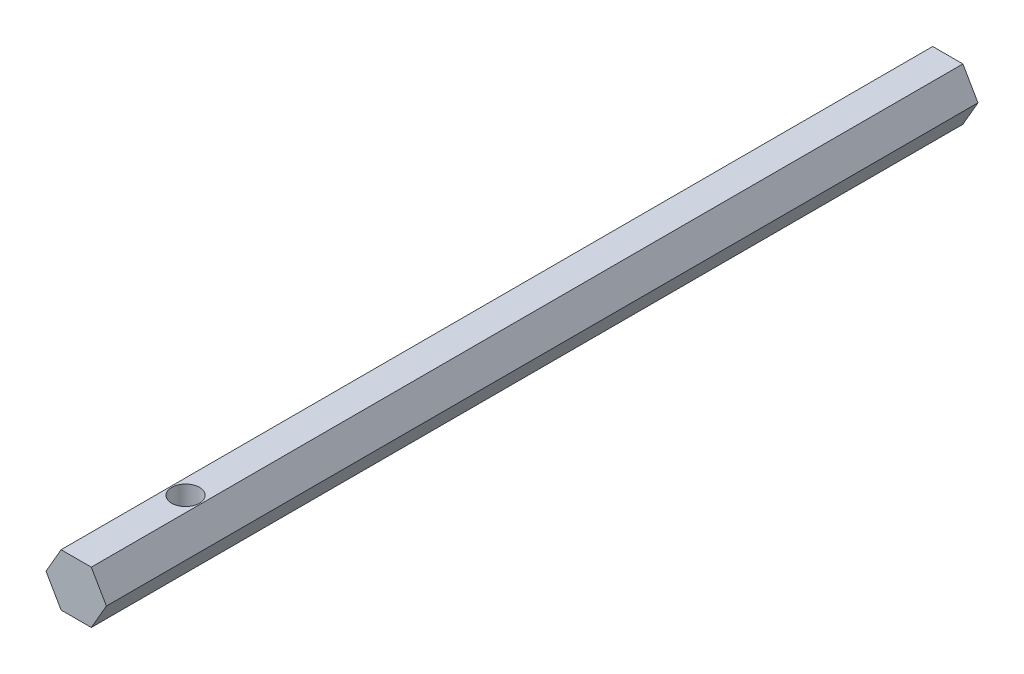
SolidWorks part; units mm, degrees
ref_plane "Front Plane" through (0, 0, 0) normal (0, 0, 1) x (1, 0, 0)
ref_plane "Top Plane" through (0, 0, 0) normal (0, 1, 0) x (1, 0, 0)
ref_plane "Right Plane" through (0, 0, 0) normal (1, 0, 0) x (0, 0, -1)
sketch "Sketch1" plane through (0, 0, 0) normal (0, 0, 1) x (1, 0, 0)
  line L1 (1.7321, 0) -> (0.866, 1.5)
  line L2 (0.866, 1.5) -> (-0.866, 1.5)
  line L3 (-0.866, 1.5) -> (-1.7321, 0)
  line L4 (-1.7321, 0) -> (-0.866, -1.5)
  line L5 (-0.866, -1.5) -> (0.866, -1.5)
  line L6 (0.866, -1.5) -> (1.7321, 0)
  circle A0 centre (0, 0) radius 1.5 construction
  dimension "D1" = 3
extrude "Boss-Extrude1" add sketch "Sketch1" along normal blind 50
ref_point "Point2"
ref_point "Point4"
ref_axis "Axis1" through (0, 0, 0) along (0, 0, 1)
hole_wizard "1/16 (0.0625) Diameter Hole1" positions "Sketch2" profile "Sketch3" hole size "1/16" standard "ANSI Inch" end condition through all
sketch "Sketch2" plane through (0, 1.5, 0) normal (0, 1, 0) x (1, 0, 0)
  point P0 (0, -43.7262)
sketch "Sketch3" plane through (0, 1.5, 43.7262) normal (1, 0, 0) x (0, 0, 1)
  line L0 (0, 0) -> (0, 3)
  line L1 (0, 3) -> (0.7937, 3)
  line L2 (0.7937, 3) -> (0.7937, 0)
  line L5 (0.7937, 0) -> (0, 0)
  line L11 (0, -6.35) -> (0, 107.95) construction
  dimension "Thru Hole Dia." = 1.5875
  dimension "Thru Hole Depth" = 3
equation "\"3mmm\"=1.23441"
